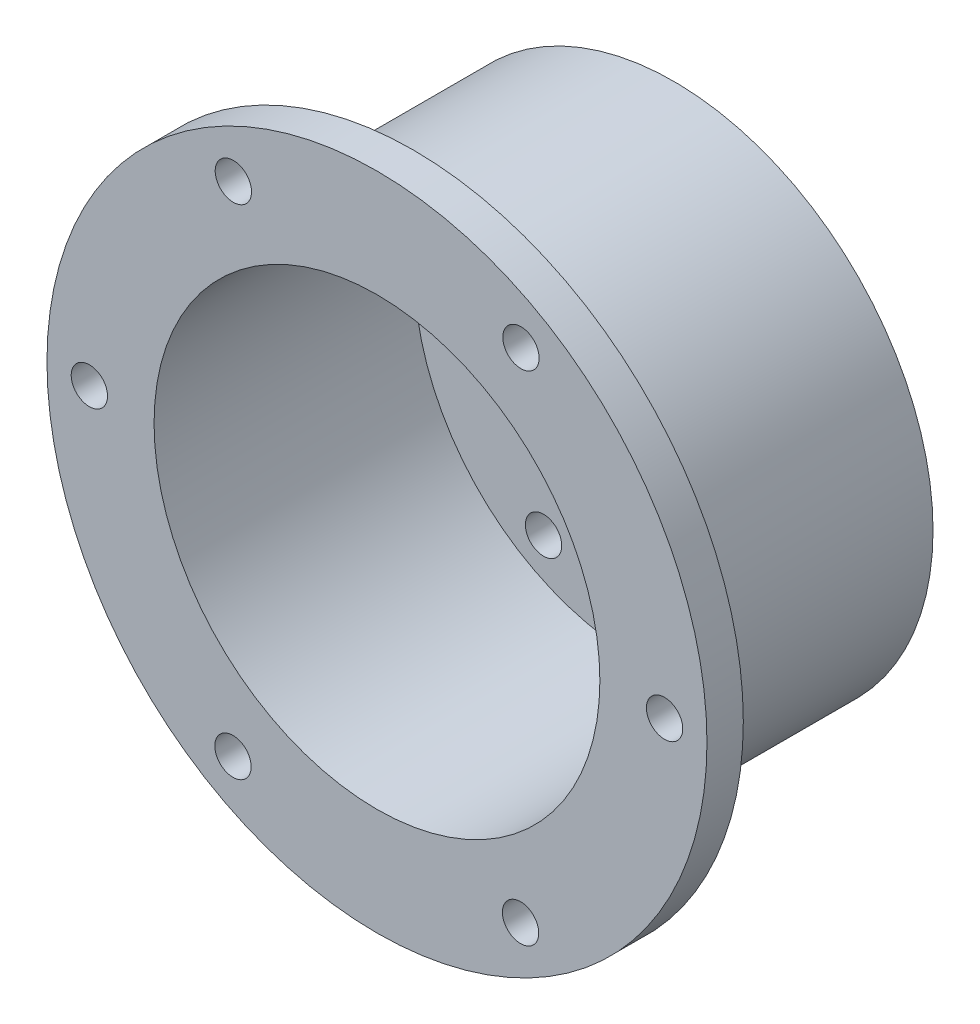
SolidWorks part; units mm, degrees
material "Resina de melamina"
ref_plane "Alzado" through (0, 0, 0) normal (0, 0, 1) x (1, 0, 0)
ref_plane "Planta" through (0, 0, 0) normal (0, 1, 0) x (1, 0, 0)
ref_plane "Vista lateral" through (0, 0, 0) normal (1, 0, 0) x (0, 0, -1)
sketch "Croquis1" plane through (0, 0, 0) normal (0, 0, 1) x (1, 0, 0)
  circle A0 centre (0, 0) radius 18.4
  circle A1 centre (0, 0) radius 21.4
  dimension "D1" = 36.8
  dimension "D2" = 42.8
extrude "Saliente-Extruir1" add sketch "Croquis1" along normal blind 24.5
sketch "Croquis2" plane through (0, 0, 0) normal (0, 0, -1) x (-1, 0, 0)
  circle A0 centre (0, 0) radius 18.4
extrude "Saliente-Extruir2" add sketch "Croquis2" against normal blind 3
sketch "Croquis3" plane through (0, 0, 24.5) normal (0, 0, 1) x (1, 0, 0)
  circle A0 centre (0, 0) radius 21.4
  circle A1 centre (0, 0) radius 27.24
  dimension "D1" = 54.48
extrude "Saliente-Extruir3" add sketch "Croquis3" against normal blind 3
sketch "Croquis4" plane through (0, 0, 0) normal (0, 0, -1) x (-1, 0, 0)
  line L0 (0, 0) -> (0, -7) construction
  line L1 (-13, 0) -> (-14, 0) construction
  line L2 (-14, 0) -> (-17, 0) construction
  circle A0 centre (0, -7) radius 6
  circle A9 centre (-15.5, 0) radius 1.5
  circle A10 centre (-7.75, 13.4234) radius 1.5
  circle A11 centre (7.75, 13.4234) radius 1.5
  circle A12 centre (15.5, 0) radius 1.5
  circle A13 centre (7.75, -13.4234) radius 1.5
  circle A14 centre (-7.75, -13.4234) radius 1.5
  dimension "D2" = 12
  dimension "D1" = 7
  dimension "D3" = 1
  dimension "D4" = 3
  dimension "D5" = 6
extrude "Cortar-Extruir1" cut sketch "Croquis4" against normal blind 3
sketch "Croquis6" plane through (0, 0, 24.5) normal (0, 0, 1) x (1, 0, 0)
  line L0 (0, 0) -> (-7.75, 13.4234) construction
  line L1 (-7.75, 13.4234) -> (-9.1877, 15.942) construction
  line L2 (-9.1877, 15.942) -> (-13.6018, 23.601) construction
  line L3 (-13.6018, 23.601) -> (-11.8541, 20.5686) construction
  circle A0 centre (0, 0) radius 18.4 construction
  circle A9 centre (0, 0) radius 27.24 construction
  circle A10 centre (-11.8541, 20.5686) radius 1.5
  circle A11 centre (11.8859, 20.5503) radius 1.5
  circle A12 centre (23.74, -0.0183) radius 1.5
  circle A13 centre (11.8541, -20.5686) radius 1.5
  circle A14 centre (-11.8859, -20.5503) radius 1.5
  circle A15 centre (-23.74, 0.0183) radius 1.5
  dimension "D1" = 3.5
  dimension "D2" = 3
  dimension "D3" = 6
extrude "Cortar-Extruir2" cut sketch "Croquis6" against normal blind 3
